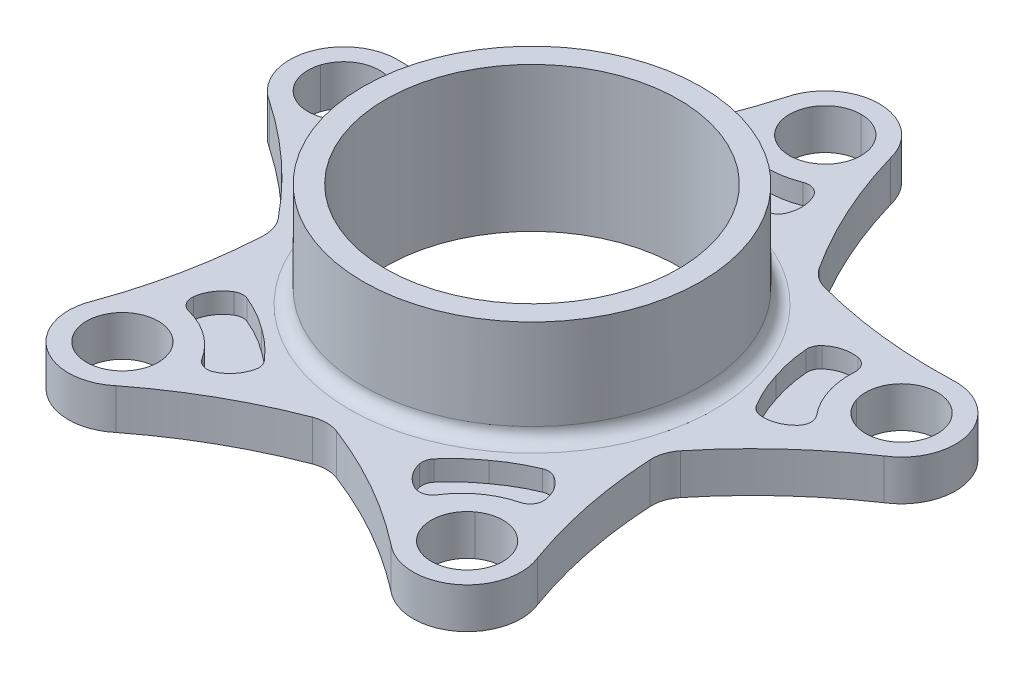
SolidWorks part; units mm, degrees
note: '?' marks a value the reader was unsure of.
ref_plane "Front Plane" through (0, 0, 0) normal (0, 0, 1) x (1, 0, 0)
ref_plane "Top Plane" through (0, 0, 0) normal (0, 1, 0) x (1, 0, 0)
ref_plane "Right Plane" through (0, 0, 0) normal (1, 0, 0) x (0, 0, -1)
sketch "Sketch1" plane through (0, 0, 0) normal (0, 1, 0) x (1, 0, 0)
  circle A0 centre (0, 0) radius 31.75
  dimension "D1" = 63.5
extrude "CenterCircleExtrude" add sketch "Sketch1" along normal blind 19.558 contours A0
sketch "Sketch2" plane through (0, 0, 0) normal (0, -1, 0) x (1, 0, 0)
  circle A0 centre (0, 0) radius 80.01
  dimension "D1" = 160.02
extrude "BaseExpand" add sketch "Sketch2" along normal blind 7.62
sketch "Sketch3" plane through (0, 19.558, 0) normal (0, 1, 0) x (1, 0, 0)
  circle A0 centre (0, 0) radius 27.559
  dimension "D1" = 55.118
extrude "CenterCut" cut sketch "Sketch3" against normal blind 27.178 contours A0
sketch "Sketch4" plane through (0, 0, 0) normal (0, 1, 0) x (1, 0, 0)
  line L0 (-52.4203, 17.0324) -> (0, 55.118) construction
  line L1 (-26.2102, 36.0752) -> (-18.6622, 25.6863) construction
  circle A0 centre (0, 55.118) radius 6.731
  circle A1 centre (52.4203, 17.0324) radius 6.731
  circle A2 centre (32.3975, -44.5914) radius 6.731
  circle A3 centre (-32.3975, -44.5914) radius 6.731
  circle A4 centre (-52.4203, 17.0324) radius 6.731
  circle A5 centre (0, 0) radius 31.75 construction
  point P14 (0, 0)
  dimension "D1" = 13.462
  dimension "D2" = 55.118
  dimension "D3" = 5
extrude "OuterCircleCut" cut sketch "Sketch4" against normal blind 7.62
sketch "Sketch8" plane through (0, 0, 0) normal (0, 1, 0) x (1, 0, 0)
  line L0 (-52.4203, 17.0324) -> (0, 55.118) construction
  line L1 (-26.2102, 36.0752) -> (-18.6622, 25.6863) construction
  line L2 (26.2102, 36.0752) -> (18.6622, 25.6863) construction
  line L3 (42.4089, -13.7795) -> (30.196, -9.8113) construction
  line L4 (0, -44.5914) -> (0, -31.75) construction
  line L5 (-42.4089, -13.7795) -> (-30.196, -9.8113) construction
  line L8 (0, 0) -> (10.16, 55.118) construction
  line L9 (10.16, 55.118) -> (-10.16, 55.118) construction
  circle A0 centre (-52.4203, 17.0324) radius 10.16
  circle A1 centre (0, 55.118) radius 10.16
  circle A2 centre (52.4203, 17.0324) radius 10.16
  circle A3 centre (32.3975, -44.5914) radius 10.16
  circle A4 centre (-32.3975, -44.5914) radius 10.16
  circle A5 centre (0, 0) radius 31.75 construction
  arc A6 (-52.4203, 27.1924) -> (-22.4362, 30.8807) centre (-48.5541, 119.4837) ccw
  arc A7 (-9.6627, 58.2576) -> (-22.4362, 30.8807) centre (-98.6317, 83.1002) cw
  arc A8 (52.4203, 27.1924) -> (22.4362, 30.8807) centre (48.5541, 119.4837) cw
  arc A9 (9.6627, 58.2576) -> (22.4362, 30.8807) centre (98.6317, 83.1002) ccw
  arc A10 (42.0603, -41.4518) -> (36.3025, -11.7954) centre (128.6398, -9.2552) cw
  arc A11 (58.3922, 8.8128) -> (36.3025, -11.7954) centre (109.5119, -68.1249) ccw
  arc A12 (-26.4256, -52.811) -> (0, -38.1707) centre (30.9496, -125.2037) cw
  arc A13 (26.4256, -52.811) -> (0, -38.1707) centre (-30.9496, -125.2037) ccw
  arc A14 (-58.3922, 8.8128) -> (-36.3025, -11.7954) centre (-109.5119, -68.1249) cw
  arc A15 (-42.0603, -41.4518) -> (-36.3025, -11.7954) centre (-128.6398, -9.2552) ccw
  point P14 (0, 0)
  point P27 (0, 0)
  point P55 (0, 0)
  point P72 (0, 0)
  dimension "D1" = 5
  dimension "D3" = 5
  dimension "D2" = 5
extrude "StarfishCut" cut sketch "Sketch8" against normal blind 7.62
fillet "Fillet8" radius 2.54 1 edges at (0, 0, 31.75)
sketch "Sketch14" plane through (0, 0, 0) normal (0, 1, 0) x (1, 0, 0)
  line L4 (0, -14.9479) -> (0, 14.9479) construction
  arc A0 (38.2121, 3.6164) -> (34.5928, 11.2399) centre (62.2856, 19.7161) cw
  arc A1 (33.0399, 19.5348) -> (34.5928, 11.2399) centre (61.9789, 20.6599) ccw
  arc A2 (41.5686, 21.0847) -> (33.0399, 19.5348) centre (38.134, 15.7437) ccw
  arc A25 (7.2074, 46.0496) -> (-7.2074, 46.0496) centre (0, 59.4776) cw
  arc A26 (-7.2074, 46.0496) -> (-8.3688, 37.4594) centre (-3.1891, 41.1327) ccw
  arc A27 (-8.3688, 37.4594) -> (0, 36.3731) centre (-0.4961, 65.3297) ccw
  arc A45 (8.3688, 37.4594) -> (0, 36.3731) centre (0.4961, 65.3297) cw
  arc A46 (7.2074, 46.0496) -> (8.3688, 37.4594) centre (3.1891, 41.1327) cw
  arc A47 (46.023, 7.3755) -> (41.5686, 21.0847) centre (56.5665, 18.3796) cw
  arc A48 (46.023, 7.3755) -> (38.2121, 3.6164) centre (40.105, 9.6777) cw
  arc A49 (15.2476, -35.2243) -> (21.3796, -29.4264) centre (37.9984, -53.1445) cw
  arc A50 (28.7886, -25.3862) -> (21.3796, -29.4264) centre (38.8012, -52.5612) ccw
  arc A51 (32.8982, -33.0185) -> (28.7886, -25.3862) centre (26.7572, -31.4026) ccw
  arc A52 (21.2364, -41.4913) -> (32.8982, -33.0185) centre (34.96, -48.1184) cw
  arc A53 (21.2364, -41.4913) -> (15.2476, -35.2243) centre (21.5972, -35.1516) cw
  arc A54 (-28.7886, -25.3862) -> (-21.3796, -29.4264) centre (-38.8012, -52.5612) cw
  arc A55 (-15.2476, -35.2243) -> (-21.3796, -29.4264) centre (-37.9984, -53.1445) ccw
  arc A56 (-21.2364, -41.4913) -> (-15.2476, -35.2243) centre (-21.5972, -35.1516) ccw
  arc A57 (-32.8982, -33.0185) -> (-21.2364, -41.4913) centre (-34.96, -48.1184) cw
  arc A58 (-32.8982, -33.0185) -> (-28.7886, -25.3862) centre (-26.7572, -31.4026) cw
  arc A59 (-33.0399, 19.5348) -> (-34.5928, 11.2399) centre (-61.9789, 20.6599) cw
  arc A60 (-38.2121, 3.6164) -> (-34.5928, 11.2399) centre (-62.2856, 19.7161) ccw
  arc A61 (-46.023, 7.3755) -> (-38.2121, 3.6164) centre (-40.105, 9.6777) ccw
  arc A62 (-41.5686, 21.0847) -> (-46.023, 7.3755) centre (-56.5665, 18.3796) cw
  arc A63 (-41.5686, 21.0847) -> (-33.0399, 19.5348) centre (-38.134, 15.7437) cw
  point P34 (0, 0)
  point P51 (0, 0)
  point P61 (0, 0)
  point P97 (0, 0)
  dimension "D1" = 6.35
  dimension "D2" = 15.24
  dimension "D4" = 5
  dimension "D3" = 28.9609
extrude "Batman Cut" cut sketch "Sketch14" against normal blind 3.81
fillet "Fillet11" radius 2.54 20 edges at (21.2364, -1.905, 41.4913) (32.8982, -1.905, 33.0185) (28.7886, -1.905, 25.3862) (15.2476, -1.905, 35.2243) (-21.2364, -1.905, 41.4913) (-32.8982, -1.905, 33.0185) (-15.2476, -1.905, 35.2243) (-28.7886, -1.905, 25.3862) (-38.2121, -1.905, -3.6164) (-46.023, -1.905, -7.3755) (-33.0399, -1.905, -19.5348) (-41.5686, -1.905, -21.0847) (38.2121, -1.905, -3.6164) (33.0399, -1.905, -19.5348) (46.023, -1.905, -7.3755) (41.5686, -1.905, -21.0847) (-8.3688, -1.905, -37.4594) (8.3688, -1.905, -37.4594) (-7.2074, -1.905, -46.0496) (7.2074, -1.905, -46.0496)
ref_axis "Axis1" through (0, -7.62, 0) along (0, 1, 0)?
fillet "Fillet12" radius 6.35 5 edges at (0, -3.81, 38.1707) (36.3025, -3.81, 11.7954) (22.4362, -3.81, -30.8807) (-22.4362, -3.81, -30.8807) (-36.3025, -3.81, 11.7954)
ref_plane "Plane1" through (0, 0, 0) normal (-0.309, 0, 0.9511) x (0.9511, 0, 0.309)
split line "Split Line1"
ref_plane "Plane2" through (0, 0, 0) normal (-0.809, 0, 0.5878) x (0.5878, 0, 0.809)
split line "Split Line2"
ref_plane "Plane3" through (0, 0, 0) normal (-0.809, 0, -0.5878) x (-0.5878, 0, 0.809)
split line "Split Line3"
ref_plane "Plane4" through (0, 0, 0) normal (0.309, 0, 0.9511) x (0.9511, 0, -0.309)
split line "Split Line4"
ref_plane "Plane5" through (0, 0, 0) normal (1, 0, 0) x (0, 0, -1)
split line "Split Line5"
